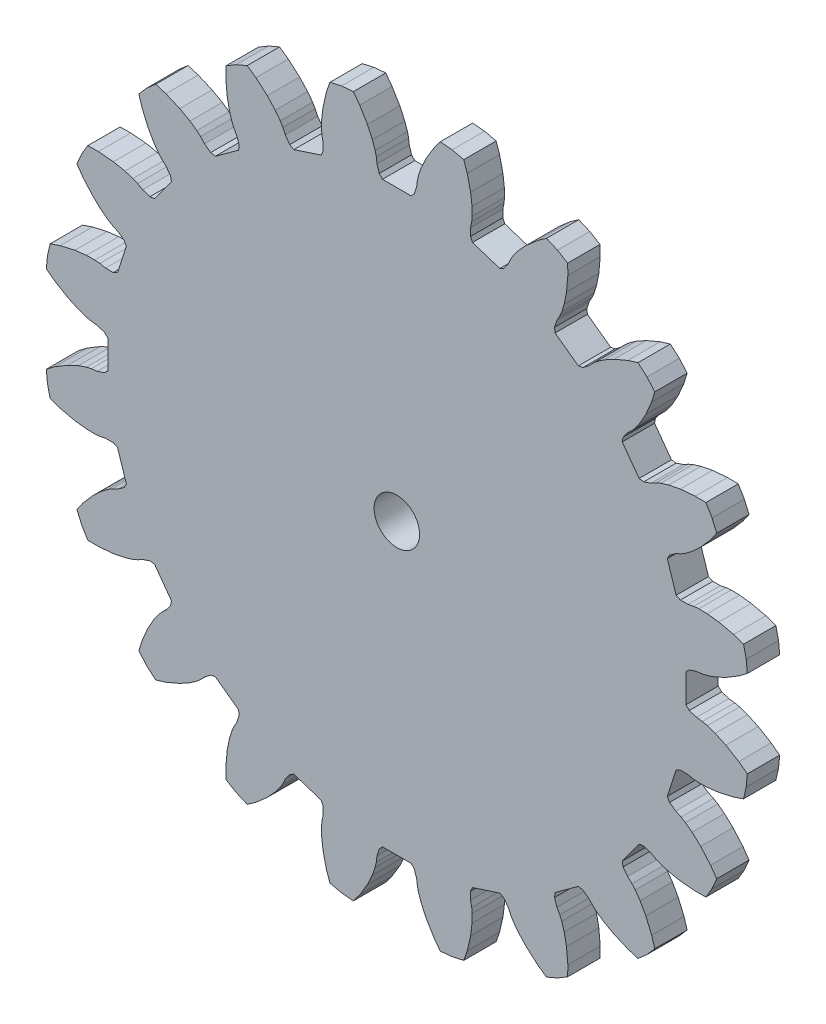
SolidWorks part; units mm, degrees
ref_plane "Front Plane" through (0, 0, 0) normal (0, 0, 1) x (1, 0, 0)
ref_plane "Top Plane" through (0, 0, 0) normal (0, 1, 0) x (1, 0, 0)
ref_plane "Right Plane" through (0, 0, 0) normal (1, 0, 0) x (0, 0, -1)
sketch "Model" plane through (0, 0, 0) normal (0, 0, 1) x (1, 0, 0)
  line L0 (-3.2331, -203.5925) -> (3.1831, -201.398)
  line L1 (3.1831, -201.398) -> (3.1831, -198.602)
  line L2 (3.1831, -198.602) -> (-3.2331, -196.4075)
  line L3 (-3.2331, -196.4075) -> (-3.2331, -193.5925)
  line L4 (-3.2331, -193.5925) -> (3.1831, -191.398)
  line L5 (3.1831, -191.398) -> (3.1831, -188.602)
  line L6 (3.1831, -188.602) -> (-3.2331, -186.4075)
  line L7 (-3.2331, -186.4075) -> (-3.2331, -183.5925)
  line L8 (-3.2331, -183.5925) -> (3.1831, -181.398)
  line L9 (3.1831, -181.398) -> (3.1831, -178.602)
  line L10 (3.1831, -178.602) -> (-3.2331, -176.4075)
  line L11 (-3.2331, -176.4075) -> (-3.2331, -173.5925)
  line L12 (-3.2331, -173.5925) -> (3.1831, -171.398)
  line L13 (3.1831, -171.398) -> (3.1831, -168.602)
  line L14 (3.1831, -168.602) -> (-3.2331, -166.4075)
  line L15 (-3.2331, -166.4075) -> (-3.2331, -163.5925)
  line L16 (-3.2331, -163.5925) -> (3.1831, -161.398)
  line L17 (3.1831, -161.398) -> (3.1831, -158.602)
  line L18 (3.1831, -158.602) -> (-3.2331, -156.4075)
  line L19 (-3.2331, -156.4075) -> (-3.2331, -153.5925)
  line L20 (-3.2331, -153.5925) -> (3.1831, -151.398)
  line L21 (3.1831, -151.398) -> (3.1831, -148.602)
  line L22 (3.1831, -148.602) -> (-3.2331, -146.4075)
  line L23 (-3.2331, -146.4075) -> (-3.2331, -143.5925)
  line L24 (-3.2331, -143.5925) -> (3.1831, -141.398)
  line L25 (3.1831, -141.398) -> (3.1831, -138.602)
  line L26 (3.1831, -138.602) -> (-3.2331, -136.4075)
  line L27 (-3.2331, -136.4075) -> (-3.2331, -133.5925)
  line L28 (-3.2331, -133.5925) -> (3.1831, -131.398)
  line L29 (3.1831, -131.398) -> (3.1831, -128.602)
  line L30 (3.1831, -128.602) -> (-3.2331, -126.4075)
  line L31 (-3.2331, -126.4075) -> (-3.2331, -123.5925)
  line L32 (-3.2331, -123.5925) -> (3.1831, -121.398)
  line L33 (3.1831, -121.398) -> (3.1831, -118.602)
  line L34 (3.1831, -118.602) -> (-3.2331, -116.4075)
  line L35 (-3.2331, -116.4075) -> (-3.2331, -113.5925)
  line L36 (-3.2331, -113.5925) -> (3.1831, -111.398)
  line L37 (3.1831, -111.398) -> (3.1831, -108.602)
  line L38 (3.1831, -108.602) -> (-3.2331, -106.4075)
  line L39 (-3.2331, -106.4075) -> (-3.2331, -103.5925)
  line L40 (-3.2331, -103.5925) -> (3.1831, -101.398)
  line L41 (3.1831, -101.398) -> (3.1831, -98.602)
  line L42 (3.1831, -98.602) -> (-3.2331, -96.4075)
  line L43 (-3.2331, -96.4075) -> (-3.2331, -93.5925)
  line L44 (-3.2331, -93.5925) -> (3.1831, -91.398)
  line L45 (3.1831, -91.398) -> (3.1831, -88.602)
  line L46 (3.1831, -88.602) -> (-3.2331, -86.4075)
  line L47 (-3.2331, -86.4075) -> (-3.2331, -83.5925)
  line L48 (-3.2331, -83.5925) -> (3.1831, -81.398)
  line L49 (3.1831, -81.398) -> (3.1831, -78.602)
  line L50 (3.1831, -78.602) -> (-3.2331, -76.4075)
  line L51 (-3.2331, -76.4075) -> (-3.2331, -73.5925)
  line L52 (-3.2331, -73.5925) -> (3.1831, -71.398)
  line L53 (3.1831, -71.398) -> (3.1831, -68.602)
  line L54 (3.1831, -68.602) -> (-3.2331, -66.4075)
  line L55 (-3.2331, -66.4075) -> (-3.2331, -63.5925)
  line L56 (-3.2331, -63.5925) -> (3.1831, -61.398)
  line L57 (3.1831, -61.398) -> (3.1831, -58.602)
  line L58 (3.1831, -58.602) -> (-3.2331, -56.4075)
  line L59 (-3.2331, -56.4075) -> (-3.2331, -53.5925)
  line L60 (-3.2331, -53.5925) -> (3.1831, -51.398)
  line L61 (3.1831, -51.398) -> (3.1831, -48.602)
  line L62 (3.1831, -48.602) -> (-3.2331, -46.4075)
  line L63 (-3.2331, -46.4075) -> (-3.2331, -43.5925)
  line L64 (-3.2331, -43.5925) -> (3.1831, -41.398)
  line L65 (3.1831, -41.398) -> (3.1831, -38.602)
  line L66 (3.1831, -38.602) -> (-3.2331, -36.4075)
  line L67 (-3.2331, -36.4075) -> (-3.2331, -33.5925)
  line L68 (-3.2331, -33.5925) -> (3.1831, -31.398)
  line L69 (3.1831, -31.398) -> (3.1831, -28.602)
  line L70 (3.1831, -28.602) -> (-3.2331, -26.4075)
  line L71 (-3.2331, -26.4075) -> (-3.2331, -23.5925)
  line L72 (-3.2331, -23.5925) -> (3.1831, -21.398)
  line L73 (3.1831, -21.398) -> (3.1831, -18.602)
  line L74 (3.1831, -18.602) -> (-3.2331, -16.4075)
  line L75 (-3.2331, -16.4075) -> (-3.2331, -13.5925)
  line L76 (-3.2331, -13.5925) -> (3.1831, -11.398)
  line L77 (3.1831, -11.398) -> (3.1831, -8.602)
  line L78 (3.1831, -8.602) -> (-3.2331, -6.4075)
  line L79 (-3.2331, -6.4075) -> (-3.2331, -3.5925)
  line L80 (-3.2331, -3.5925) -> (3.1831, -1.398)
  line L81 (3.1831, -1.398) -> (3.1831, 1.398)
  line L82 (3.1831, 1.398) -> (-3.2331, 3.5925)
  line L83 (-3.2331, 3.5925) -> (-3.2331, 6.4075)
  line L84 (-3.2331, 6.4075) -> (3.1831, 8.602)
  line L85 (3.1831, 8.602) -> (3.1831, 11.398)
  line L86 (3.1831, 11.398) -> (-3.2331, 13.5925)
  line L87 (-3.2331, 13.5925) -> (-3.2331, 16.4075)
  line L88 (-3.2331, 16.4075) -> (3.1831, 18.602)
  line L89 (3.1831, 18.602) -> (3.1831, 21.398)
  line L90 (3.1831, 21.398) -> (-3.2331, 23.5925)
  line L91 (-3.2331, 23.5925) -> (-3.2331, 26.4075)
  line L92 (-3.2331, 26.4075) -> (3.1831, 28.602)
  line L93 (3.1831, 28.602) -> (3.1831, 31.398)
  line L94 (3.1831, 31.398) -> (-3.2331, 33.5925)
  line L95 (-3.2331, 33.5925) -> (-3.2331, 36.4075)
  line L96 (-3.2331, 36.4075) -> (3.1831, 38.602)
  line L97 (3.1831, 38.602) -> (3.1831, 41.398)
  line L98 (3.1831, 41.398) -> (-3.2331, 43.5925)
  line L99 (-3.2331, 43.5925) -> (-3.2331, 46.4075)
  line L100 (-3.2331, 46.4075) -> (3.1831, 48.602)
  line L101 (3.1831, 48.602) -> (3.1831, 51.398)
  line L102 (3.1831, 51.398) -> (-3.2331, 53.5925)
  line L103 (-3.2331, 53.5925) -> (-3.2331, 56.4075)
  line L104 (-3.2331, 56.4075) -> (3.1831, 58.602)
  line L105 (3.1831, 58.602) -> (3.1831, 61.398)
  line L106 (3.1831, 61.398) -> (-3.2331, 63.5925)
  line L107 (-3.2331, 63.5925) -> (-3.2331, 66.4075)
  line L108 (-3.2331, 66.4075) -> (3.1831, 68.602)
  line L109 (3.1831, 68.602) -> (3.1831, 71.398)
  line L110 (3.1831, 71.398) -> (-3.2331, 73.5925)
  line L111 (-3.2331, 73.5925) -> (-3.2331, 76.4075)
  line L112 (-3.2331, 76.4075) -> (3.1831, 78.602)
  line L113 (3.1831, 78.602) -> (3.1831, 81.398)
  line L114 (3.1831, 81.398) -> (-3.2331, 83.5925)
  line L115 (-3.2331, 83.5925) -> (-3.2331, 86.4075)
  line L116 (-3.2331, 86.4075) -> (3.1831, 88.602)
  line L117 (3.1831, 88.602) -> (3.1831, 91.398)
  line L118 (3.1831, 91.398) -> (-3.2331, 93.5925)
  line L119 (-3.2331, 93.5925) -> (-3.2331, 96.4075)
  line L120 (-3.2331, 96.4075) -> (3.1831, 98.602)
  line L121 (3.1831, 98.602) -> (3.1831, 101.398)
  line L122 (3.1831, 101.398) -> (-3.2331, 103.5925)
  line L123 (-3.2331, 103.5925) -> (-3.2331, 106.4075)
  line L124 (-3.2331, 106.4075) -> (3.1831, 108.602)
  line L125 (3.1831, 108.602) -> (3.1831, 111.398)
  line L126 (3.1831, 111.398) -> (-3.2331, 113.5925)
  line L127 (-3.2331, 113.5925) -> (-3.2331, 116.4075)
  line L128 (-3.2331, 116.4075) -> (3.1831, 118.602)
  line L129 (3.1831, 118.602) -> (3.1831, 121.398)
  line L130 (3.1831, 121.398) -> (-3.2331, 123.5925)
  line L131 (-3.2331, 123.5925) -> (-3.2331, 126.4075)
  line L132 (-3.2331, 126.4075) -> (3.1831, 128.602)
  line L133 (3.1831, 128.602) -> (3.1831, 131.398)
  line L134 (3.1831, 131.398) -> (-3.2331, 133.5925)
  line L135 (-3.2331, 133.5925) -> (-3.2331, 136.4075)
  line L136 (-3.2331, 136.4075) -> (3.1831, 138.602)
  line L137 (3.1831, 138.602) -> (3.1831, 141.398)
  line L138 (3.1831, 141.398) -> (-3.2331, 143.5925)
  line L139 (-3.2331, 143.5925) -> (-3.2331, 146.4075)
  line L140 (-3.2331, 146.4075) -> (3.1831, 148.602)
  line L141 (3.1831, 148.602) -> (3.1831, 151.398)
  line L142 (3.1831, 151.398) -> (-3.2331, 153.5925)
  line L143 (-3.2331, 153.5925) -> (-3.2331, 156.4075)
  line L144 (-3.2331, 156.4075) -> (3.1831, 158.602)
  line L145 (3.1831, 158.602) -> (3.1831, 161.398)
  line L146 (3.1831, 161.398) -> (-3.2331, 163.5925)
  line L147 (-3.2331, 163.5925) -> (-3.2331, 166.4075)
  line L148 (-3.2331, 166.4075) -> (3.1831, 168.602)
  line L149 (3.1831, 168.602) -> (3.1831, 171.398)
  line L150 (3.1831, 171.398) -> (-3.2331, 173.5925)
  line L151 (-3.2331, 173.5925) -> (-3.2331, 176.4075)
  line L152 (-3.2331, 176.4075) -> (3.1831, 178.602)
  line L153 (3.1831, 178.602) -> (3.1831, 181.398)
  line L154 (3.1831, 181.398) -> (-3.2331, 183.5925)
  line L155 (-3.2331, 183.5925) -> (-3.2331, 186.4075)
  line L156 (-3.2331, 186.4075) -> (3.1831, 188.602)
  line L157 (3.1831, 188.602) -> (3.1831, 191.398)
  line L158 (3.1831, 191.398) -> (-3.2331, 193.5925)
  line L159 (-3.2331, 193.5925) -> (-3.2331, 196.4075)
  line L160 (-3.2331, 196.4075) -> (3.1831, 198.602)
  line L161 (3.1831, 198.602) -> (3.1831, 201.398)
  line L162 (3.1831, 201.398) -> (-3.2331, 203.5925)
  line L163 (-3.2331, 203.5925) -> (-3.2331, 205)
  line L164 (-3.2331, 205) -> (-15.9655, 205)
  line L165 (-15.9655, 205) -> (-15.9655, -205)
  line L166 (-15.9655, -205) -> (-3.2331, -205)
  line L167 (-3.2331, -205) -> (-3.2331, -203.5925)
  line L168 (-2.4761, 6.6265) -> (-2.752, 5.4774)
  line L169 (-2.752, 5.4774) -> (-2.8447, 4.2993)
  line L170 (-2.8447, 4.2993) -> (-2.0018, 3.6669)
  line L171 (-2.0018, 3.6669) -> (-0.7228, 2.9019)
  line L172 (-0.7228, 2.9019) -> (0.3292, 2.414)
  line L173 (0.3292, 2.414) -> (1.1138, 2.1457)
  line L174 (1.1138, 2.1457) -> (1.5998, 2.0345)
  line L175 (1.5998, 2.0345) -> (2.1765, 1.9649)
  line L176 (2.1765, 1.9649) -> (2.8928, 1.7388)
  line L177 (2.8928, 1.7388) -> (3.2331, 1.4208)
  line L178 (3.2331, 1.4208) -> (3.2331, -1.4208)
  line L179 (3.2331, -1.4208) -> (2.8928, -1.7388)
  line L180 (2.8928, -1.7388) -> (2.1765, -1.9649)
  line L181 (2.1765, -1.9649) -> (1.5998, -2.0345)
  line L182 (1.5998, -2.0345) -> (1.1138, -2.1457)
  line L183 (1.1138, -2.1457) -> (0.3292, -2.414)
  line L184 (0.3292, -2.414) -> (-0.7228, -2.9019)
  line L185 (-0.7228, -2.9019) -> (-2.0018, -3.6669)
  line L186 (-2.0018, -3.6669) -> (-2.8447, -4.2993)
  line L187 (-2.8447, -4.2993) -> (-2.752, -5.4774)
  line L188 (-2.752, -5.4774) -> (-2.4761, -6.6265)
  line L189 (-2.4761, -6.6265) -> (-1.4791, -6.9675)
  line L190 (-1.4791, -6.9675) -> (-0.0263, -7.2998)
  line L191 (-0.0263, -7.2998) -> (1.1251, -7.4387)
  line L192 (1.1251, -7.4387) -> (1.9541, -7.4515)
  line L193 (1.9541, -7.4515) -> (2.4507, -7.407)
  line L194 (2.4507, -7.407) -> (3.0207, -7.295)
  line L195 (3.0207, -7.295) -> (3.7718, -7.2887)
  line L196 (3.7718, -7.2887) -> (4.1937, -7.486)
  line L197 (4.1937, -7.486) -> (5.0718, -10.1885)
  line L198 (5.0718, -10.1885) -> (4.8465, -10.5961)
  line L199 (4.8465, -10.5961) -> (4.2351, -11.0325)
  line L200 (4.2351, -11.0325) -> (3.7081, -11.2769)
  line L201 (3.7081, -11.2769) -> (3.2802, -11.5328)
  line L202 (3.2802, -11.5328) -> (2.617, -12.0304)
  line L203 (2.617, -12.0304) -> (1.7672, -12.8196)
  line L204 (1.7672, -12.8196) -> (0.7872, -13.9423)
  line L205 (0.7872, -13.9423) -> (0.181, -14.8043)
  line L206 (0.181, -14.8043) -> (0.6332, -15.8961)
  line L207 (0.6332, -15.8961) -> (1.2507, -16.9037)
  line L208 (1.2507, -16.9037) -> (2.3043, -16.9199)
  line L209 (2.3043, -16.9199) -> (3.7887, -16.7869)
  line L210 (3.7887, -16.7869) -> (4.9266, -16.5633)
  line L211 (4.9266, -16.5633) -> (5.719, -16.3192)
  line L212 (5.719, -16.3192) -> (6.1775, -16.1235)
  line L213 (6.1775, -16.1235) -> (6.6851, -15.8408)
  line L214 (6.6851, -15.8408) -> (7.3975, -15.6027)
  line L215 (7.3975, -15.6027) -> (7.8597, -15.66)
  line L216 (7.8597, -15.66) -> (9.5299, -17.9589)
  line L217 (9.5299, -17.9589) -> (9.4416, -18.4162)
  line L218 (9.4416, -18.4162) -> (8.995, -19.0201)
  line L219 (8.995, -19.0201) -> (8.5693, -19.4154)
  line L220 (8.5693, -19.4154) -> (8.2414, -19.791)
  line L221 (8.2414, -19.791) -> (7.7645, -20.4692)
  line L222 (7.7645, -20.4692) -> (7.2001, -21.4824)
  line L223 (7.2001, -21.4824) -> (6.615, -22.853)
  line L224 (6.615, -22.853) -> (6.3048, -23.8601)
  line L225 (6.3048, -23.8601) -> (7.0723, -24.7587)
  line L226 (7.0723, -24.7587) -> (7.9709, -25.5262)
  line L227 (7.9709, -25.5262) -> (8.978, -25.216)
  line L228 (8.978, -25.216) -> (10.3486, -24.6309)
  line L229 (10.3486, -24.6309) -> (11.3618, -24.0665)
  line L230 (11.3618, -24.0665) -> (12.04, -23.5896)
  line L231 (12.04, -23.5896) -> (12.4155, -23.2617)
  line L232 (12.4155, -23.2617) -> (12.8109, -22.836)
  line L233 (12.8109, -22.836) -> (13.4148, -22.3894)
  line L234 (13.4148, -22.3894) -> (13.8721, -22.301)
  line L235 (13.8721, -22.301) -> (16.171, -23.9713)
  line L236 (16.171, -23.9713) -> (16.2283, -24.4335)
  line L237 (16.2283, -24.4335) -> (15.9902, -25.1459)
  line L238 (15.9902, -25.1459) -> (15.7075, -25.6535)
  line L239 (15.7075, -25.6535) -> (15.5117, -26.112)
  line L240 (15.5117, -26.112) -> (15.2677, -26.9044)
  line L241 (15.2677, -26.9044) -> (15.0441, -28.0423)
  line L242 (15.0441, -28.0423) -> (14.9111, -29.5267)
  line L243 (14.9111, -29.5267) -> (14.9273, -30.5803)
  line L244 (14.9273, -30.5803) -> (15.9349, -31.1978)
  line L245 (15.9349, -31.1978) -> (17.0267, -31.65)
  line L246 (17.0267, -31.65) -> (17.8887, -31.0438)
  line L247 (17.8887, -31.0438) -> (19.0114, -30.0638)
  line L248 (19.0114, -30.0638) -> (19.8006, -29.214)
  line L249 (19.8006, -29.214) -> (20.2982, -28.5508)
  line L250 (20.2982, -28.5508) -> (20.5541, -28.1229)
  line L251 (20.5541, -28.1229) -> (20.7985, -27.5959)
  line L252 (20.7985, -27.5959) -> (21.2349, -26.9845)
  line L253 (21.2349, -26.9845) -> (21.6425, -26.7592)
  line L254 (21.6425, -26.7592) -> (24.345, -27.6373)
  line L255 (24.345, -27.6373) -> (24.5423, -28.0592)
  line L256 (24.5423, -28.0592) -> (24.536, -28.8102)
  line L257 (24.536, -28.8102) -> (24.424, -29.3803)
  line L258 (24.424, -29.3803) -> (24.3795, -29.8769)
  line L259 (24.3795, -29.8769) -> (24.3923, -30.7059)
  line L260 (24.3923, -30.7059) -> (24.5312, -31.8573)
  line L261 (24.5312, -31.8573) -> (24.8635, -33.3101)
  line L262 (24.8635, -33.3101) -> (25.2045, -34.3071)
  line L263 (25.2045, -34.3071) -> (26.3536, -34.583)
  line L264 (26.3536, -34.583) -> (27.5317, -34.6757)
  line L265 (27.5317, -34.6757) -> (28.1641, -33.8328)
  line L266 (28.1641, -33.8328) -> (28.929, -32.5538)
  line L267 (28.929, -32.5538) -> (29.417, -31.5017)
  line L268 (29.417, -31.5017) -> (29.6853, -30.7172)
  line L269 (29.6853, -30.7172) -> (29.7965, -30.2312)
  line L270 (29.7965, -30.2312) -> (29.8661, -29.6544)
  line L271 (29.8661, -29.6544) -> (30.0922, -28.9382)
  line L272 (30.0922, -28.9382) -> (30.4102, -28.5979)
  line L273 (30.4102, -28.5979) -> (33.2518, -28.5979)
  line L274 (33.2518, -28.5979) -> (33.5698, -28.9382)
  line L275 (33.5698, -28.9382) -> (33.7959, -29.6544)
  line L276 (33.7959, -29.6544) -> (33.8655, -30.2312)
  line L277 (33.8655, -30.2312) -> (33.9767, -30.7172)
  line L278 (33.9767, -30.7172) -> (34.245, -31.5017)
  line L279 (34.245, -31.5017) -> (34.7329, -32.5538)
  line L280 (34.7329, -32.5538) -> (35.4979, -33.8328)
  line L281 (35.4979, -33.8328) -> (36.1303, -34.6757)
  line L282 (36.1303, -34.6757) -> (37.3084, -34.583)
  line L283 (37.3084, -34.583) -> (38.4575, -34.3071)
  line L284 (38.4575, -34.3071) -> (38.7985, -33.3101)
  line L285 (38.7985, -33.3101) -> (39.1308, -31.8573)
  line L286 (39.1308, -31.8573) -> (39.2697, -30.7059)
  line L287 (39.2697, -30.7059) -> (39.2825, -29.8769)
  line L288 (39.2825, -29.8769) -> (39.238, -29.3803)
  line L289 (39.238, -29.3803) -> (39.126, -28.8102)
  line L290 (39.126, -28.8102) -> (39.1197, -28.0592)
  line L291 (39.1197, -28.0592) -> (39.3169, -27.6373)
  line L292 (39.3169, -27.6373) -> (42.0195, -26.7592)
  line L293 (42.0195, -26.7592) -> (42.4271, -26.9845)
  line L294 (42.4271, -26.9845) -> (42.8635, -27.5959)
  line L295 (42.8635, -27.5959) -> (43.1079, -28.1229)
  line L296 (43.1079, -28.1229) -> (43.3638, -28.5508)
  line L297 (43.3638, -28.5508) -> (43.8614, -29.214)
  line L298 (43.8614, -29.214) -> (44.6506, -30.0638)
  line L299 (44.6506, -30.0638) -> (45.7733, -31.0438)
  line L300 (45.7733, -31.0438) -> (46.6353, -31.65)
  line L301 (46.6353, -31.65) -> (47.7271, -31.1978)
  line L302 (47.7271, -31.1978) -> (48.7347, -30.5803)
  line L303 (48.7347, -30.5803) -> (48.7509, -29.5267)
  line L304 (48.7509, -29.5267) -> (48.6179, -28.0423)
  line L305 (48.6179, -28.0423) -> (48.3943, -26.9044)
  line L306 (48.3943, -26.9044) -> (48.1502, -26.112)
  line L307 (48.1502, -26.112) -> (47.9545, -25.6535)
  line L308 (47.9545, -25.6535) -> (47.6718, -25.1459)
  line L309 (47.6718, -25.1459) -> (47.4337, -24.4335)
  line L310 (47.4337, -24.4335) -> (47.4909, -23.9713)
  line L311 (47.4909, -23.9713) -> (49.7899, -22.301)
  line L312 (49.7899, -22.301) -> (50.2472, -22.3894)
  line L313 (50.2472, -22.3894) -> (50.8511, -22.836)
  line L314 (50.8511, -22.836) -> (51.2464, -23.2617)
  line L315 (51.2464, -23.2617) -> (51.622, -23.5896)
  line L316 (51.622, -23.5896) -> (52.3002, -24.0665)
  line L317 (52.3002, -24.0665) -> (53.3134, -24.6309)
  line L318 (53.3134, -24.6309) -> (54.684, -25.216)
  line L319 (54.684, -25.216) -> (55.6911, -25.5262)
  line L320 (55.6911, -25.5262) -> (56.5897, -24.7587)
  line L321 (56.5897, -24.7587) -> (57.3572, -23.8601)
  line L322 (57.3572, -23.8601) -> (57.047, -22.853)
  line L323 (57.047, -22.853) -> (56.4619, -21.4824)
  line L324 (56.4619, -21.4824) -> (55.8975, -20.4692)
  line L325 (55.8975, -20.4692) -> (55.4206, -19.791)
  line L326 (55.4206, -19.791) -> (55.0927, -19.4154)
  line L327 (55.0927, -19.4154) -> (54.667, -19.0201)
  line L328 (54.667, -19.0201) -> (54.2204, -18.4162)
  line L329 (54.2204, -18.4162) -> (54.132, -17.9589)
  line L330 (54.132, -17.9589) -> (55.8023, -15.66)
  line L331 (55.8023, -15.66) -> (56.2645, -15.6027)
  line L332 (56.2645, -15.6027) -> (56.9769, -15.8408)
  line L333 (56.9769, -15.8408) -> (57.4844, -16.1235)
  line L334 (57.4844, -16.1235) -> (57.943, -16.3192)
  line L335 (57.943, -16.3192) -> (58.7353, -16.5633)
  line L336 (58.7353, -16.5633) -> (59.8733, -16.7869)
  line L337 (59.8733, -16.7869) -> (61.3577, -16.9199)
  line L338 (61.3577, -16.9199) -> (62.4113, -16.9037)
  line L339 (62.4113, -16.9037) -> (63.0288, -15.8961)
  line L340 (63.0288, -15.8961) -> (63.481, -14.8043)
  line L341 (63.481, -14.8043) -> (62.8748, -13.9423)
  line L342 (62.8748, -13.9423) -> (61.8948, -12.8196)
  line L343 (61.8948, -12.8196) -> (61.045, -12.0304)
  line L344 (61.045, -12.0304) -> (60.3818, -11.5328)
  line L345 (60.3818, -11.5328) -> (59.9539, -11.2769)
  line L346 (59.9539, -11.2769) -> (59.4268, -11.0325)
  line L347 (59.4268, -11.0325) -> (58.8155, -10.5961)
  line L348 (58.8155, -10.5961) -> (58.5901, -10.1885)
  line L349 (58.5901, -10.1885) -> (59.4683, -7.486)
  line L350 (59.4683, -7.486) -> (59.8901, -7.2887)
  line L351 (59.8901, -7.2887) -> (60.6412, -7.295)
  line L352 (60.6412, -7.295) -> (61.2113, -7.407)
  line L353 (61.2113, -7.407) -> (61.7079, -7.4515)
  line L354 (61.7079, -7.4515) -> (62.5369, -7.4387)
  line L355 (62.5369, -7.4387) -> (63.6883, -7.2998)
  line L356 (63.6883, -7.2998) -> (65.141, -6.9675)
  line L357 (65.141, -6.9675) -> (66.1381, -6.6265)
  line L358 (66.1381, -6.6265) -> (66.414, -5.4774)
  line L359 (66.414, -5.4774) -> (66.5067, -4.2993)
  line L360 (66.5067, -4.2993) -> (65.6638, -3.6669)
  line L361 (65.6638, -3.6669) -> (64.3848, -2.9019)
  line L362 (64.3848, -2.9019) -> (63.3327, -2.414)
  line L363 (63.3327, -2.414) -> (62.5482, -2.1457)
  line L364 (62.5482, -2.1457) -> (62.0622, -2.0345)
  line L365 (62.0622, -2.0345) -> (61.4854, -1.9649)
  line L366 (61.4854, -1.9649) -> (60.7692, -1.7388)
  line L367 (60.7692, -1.7388) -> (60.4289, -1.4208)
  line L368 (60.4289, -1.4208) -> (60.4289, 1.4208)
  line L369 (60.4289, 1.4208) -> (60.7692, 1.7388)
  line L370 (60.7692, 1.7388) -> (61.4854, 1.9649)
  line L371 (61.4854, 1.9649) -> (62.0622, 2.0345)
  line L372 (62.0622, 2.0345) -> (62.5482, 2.1457)
  line L373 (62.5482, 2.1457) -> (63.3327, 2.414)
  line L374 (63.3327, 2.414) -> (64.3848, 2.9019)
  line L375 (64.3848, 2.9019) -> (65.6638, 3.6669)
  line L376 (65.6638, 3.6669) -> (66.5067, 4.2993)
  line L377 (66.5067, 4.2993) -> (66.414, 5.4774)
  line L378 (66.414, 5.4774) -> (66.1381, 6.6265)
  line L379 (66.1381, 6.6265) -> (65.141, 6.9675)
  line L380 (65.141, 6.9675) -> (63.6883, 7.2998)
  line L381 (63.6883, 7.2998) -> (62.5369, 7.4387)
  line L382 (62.5369, 7.4387) -> (61.7079, 7.4515)
  line L383 (61.7079, 7.4515) -> (61.2113, 7.407)
  line L384 (61.2113, 7.407) -> (60.6412, 7.295)
  line L385 (60.6412, 7.295) -> (59.8901, 7.2887)
  line L386 (59.8901, 7.2887) -> (59.4683, 7.486)
  line L387 (59.4683, 7.486) -> (58.5901, 10.1885)
  line L388 (58.5901, 10.1885) -> (58.8155, 10.5961)
  line L389 (58.8155, 10.5961) -> (59.4268, 11.0325)
  line L390 (59.4268, 11.0325) -> (59.9539, 11.2769)
  line L391 (59.9539, 11.2769) -> (60.3818, 11.5328)
  line L392 (60.3818, 11.5328) -> (61.045, 12.0304)
  line L393 (61.045, 12.0304) -> (61.8948, 12.8196)
  line L394 (61.8948, 12.8196) -> (62.8748, 13.9423)
  line L395 (62.8748, 13.9423) -> (63.481, 14.8043)
  line L396 (63.481, 14.8043) -> (63.0288, 15.8961)
  line L397 (63.0288, 15.8961) -> (62.4113, 16.9037)
  line L398 (62.4113, 16.9037) -> (61.3577, 16.9199)
  line L399 (61.3577, 16.9199) -> (59.8733, 16.7869)
  line L400 (59.8733, 16.7869) -> (58.7353, 16.5633)
  line L401 (58.7353, 16.5633) -> (57.943, 16.3192)
  line L402 (57.943, 16.3192) -> (57.4844, 16.1235)
  line L403 (57.4844, 16.1235) -> (56.9769, 15.8408)
  line L404 (56.9769, 15.8408) -> (56.2645, 15.6027)
  line L405 (56.2645, 15.6027) -> (55.8023, 15.66)
  line L406 (55.8023, 15.66) -> (54.132, 17.9589)
  line L407 (54.132, 17.9589) -> (54.2204, 18.4162)
  line L408 (54.2204, 18.4162) -> (54.667, 19.0201)
  line L409 (54.667, 19.0201) -> (55.0927, 19.4154)
  line L410 (55.0927, 19.4154) -> (55.4206, 19.791)
  line L411 (55.4206, 19.791) -> (55.8975, 20.4692)
  line L412 (55.8975, 20.4692) -> (56.4619, 21.4824)
  line L413 (56.4619, 21.4824) -> (57.047, 22.853)
  line L414 (57.047, 22.853) -> (57.3572, 23.8601)
  line L415 (57.3572, 23.8601) -> (56.5897, 24.7587)
  line L416 (56.5897, 24.7587) -> (55.6911, 25.5262)
  line L417 (55.6911, 25.5262) -> (54.684, 25.216)
  line L418 (54.684, 25.216) -> (53.3134, 24.6309)
  line L419 (53.3134, 24.6309) -> (52.3002, 24.0665)
  line L420 (52.3002, 24.0665) -> (51.622, 23.5896)
  line L421 (51.622, 23.5896) -> (51.2464, 23.2617)
  line L422 (51.2464, 23.2617) -> (50.8511, 22.836)
  line L423 (50.8511, 22.836) -> (50.2472, 22.3894)
  line L424 (50.2472, 22.3894) -> (49.7899, 22.301)
  line L425 (49.7899, 22.301) -> (47.4909, 23.9713)
  line L426 (47.4909, 23.9713) -> (47.4337, 24.4335)
  line L427 (47.4337, 24.4335) -> (47.6718, 25.1459)
  line L428 (47.6718, 25.1459) -> (47.9545, 25.6535)
  line L429 (47.9545, 25.6535) -> (48.1502, 26.112)
  line L430 (48.1502, 26.112) -> (48.3943, 26.9044)
  line L431 (48.3943, 26.9044) -> (48.6179, 28.0423)
  line L432 (48.6179, 28.0423) -> (48.7509, 29.5267)
  line L433 (48.7509, 29.5267) -> (48.7347, 30.5803)
  line L434 (48.7347, 30.5803) -> (47.7271, 31.1978)
  line L435 (47.7271, 31.1978) -> (46.6353, 31.65)
  line L436 (46.6353, 31.65) -> (45.7733, 31.0438)
  line L437 (45.7733, 31.0438) -> (44.6506, 30.0638)
  line L438 (44.6506, 30.0638) -> (43.8614, 29.214)
  line L439 (43.8614, 29.214) -> (43.3638, 28.5508)
  line L440 (43.3638, 28.5508) -> (43.1079, 28.1229)
  line L441 (43.1079, 28.1229) -> (42.8635, 27.5959)
  line L442 (42.8635, 27.5959) -> (42.4271, 26.9845)
  line L443 (42.4271, 26.9845) -> (42.0195, 26.7592)
  line L444 (42.0195, 26.7592) -> (39.3169, 27.6373)
  line L445 (39.3169, 27.6373) -> (39.1197, 28.0592)
  line L446 (39.1197, 28.0592) -> (39.126, 28.8102)
  line L447 (39.126, 28.8102) -> (39.238, 29.3803)
  line L448 (39.238, 29.3803) -> (39.2825, 29.8769)
  line L449 (39.2825, 29.8769) -> (39.2697, 30.7059)
  line L450 (39.2697, 30.7059) -> (39.1308, 31.8573)
  line L451 (39.1308, 31.8573) -> (38.7985, 33.3101)
  line L452 (38.7985, 33.3101) -> (38.4575, 34.3071)
  line L453 (38.4575, 34.3071) -> (37.3084, 34.583)
  line L454 (37.3084, 34.583) -> (36.1303, 34.6757)
  line L455 (36.1303, 34.6757) -> (35.4979, 33.8328)
  line L456 (35.4979, 33.8328) -> (34.7329, 32.5538)
  line L457 (34.7329, 32.5538) -> (34.245, 31.5017)
  line L458 (34.245, 31.5017) -> (33.9767, 30.7172)
  line L459 (33.9767, 30.7172) -> (33.8655, 30.2312)
  line L460 (33.8655, 30.2312) -> (33.7959, 29.6544)
  line L461 (33.7959, 29.6544) -> (33.5698, 28.9382)
  line L462 (33.5698, 28.9382) -> (33.2518, 28.5979)
  line L463 (33.2518, 28.5979) -> (30.4102, 28.5979)
  line L464 (30.4102, 28.5979) -> (30.0922, 28.9382)
  line L465 (30.0922, 28.9382) -> (29.8661, 29.6544)
  line L466 (29.8661, 29.6544) -> (29.7965, 30.2312)
  line L467 (29.7965, 30.2312) -> (29.6853, 30.7172)
  line L468 (29.6853, 30.7172) -> (29.417, 31.5017)
  line L469 (29.417, 31.5017) -> (28.929, 32.5538)
  line L470 (28.929, 32.5538) -> (28.1641, 33.8328)
  line L471 (28.1641, 33.8328) -> (27.5317, 34.6757)
  line L472 (27.5317, 34.6757) -> (26.3536, 34.583)
  line L473 (26.3536, 34.583) -> (25.2045, 34.3071)
  line L474 (25.2045, 34.3071) -> (24.8635, 33.3101)
  line L475 (24.8635, 33.3101) -> (24.5312, 31.8573)
  line L476 (24.5312, 31.8573) -> (24.3923, 30.7059)
  line L477 (24.3923, 30.7059) -> (24.3795, 29.8769)
  line L478 (24.3795, 29.8769) -> (24.424, 29.3803)
  line L479 (24.424, 29.3803) -> (24.536, 28.8102)
  line L480 (24.536, 28.8102) -> (24.5423, 28.0592)
  line L481 (24.5423, 28.0592) -> (24.345, 27.6373)
  line L482 (24.345, 27.6373) -> (21.6425, 26.7592)
  line L483 (21.6425, 26.7592) -> (21.2349, 26.9845)
  line L484 (21.2349, 26.9845) -> (20.7985, 27.5959)
  line L485 (20.7985, 27.5959) -> (20.5541, 28.1229)
  line L486 (20.5541, 28.1229) -> (20.2982, 28.5508)
  line L487 (20.2982, 28.5508) -> (19.8006, 29.214)
  line L488 (19.8006, 29.214) -> (19.0114, 30.0638)
  line L489 (19.0114, 30.0638) -> (17.8887, 31.0438)
  line L490 (17.8887, 31.0438) -> (17.0267, 31.65)
  line L491 (17.0267, 31.65) -> (15.9349, 31.1978)
  line L492 (15.9349, 31.1978) -> (14.9273, 30.5803)
  line L493 (14.9273, 30.5803) -> (14.9111, 29.5267)
  line L494 (14.9111, 29.5267) -> (15.0441, 28.0423)
  line L495 (15.0441, 28.0423) -> (15.2677, 26.9044)
  line L496 (15.2677, 26.9044) -> (15.5117, 26.112)
  line L497 (15.5117, 26.112) -> (15.7075, 25.6535)
  line L498 (15.7075, 25.6535) -> (15.9902, 25.1459)
  line L499 (15.9902, 25.1459) -> (16.2283, 24.4335)
  line L500 (16.2283, 24.4335) -> (16.171, 23.9713)
  line L501 (16.171, 23.9713) -> (13.8721, 22.301)
  line L502 (13.8721, 22.301) -> (13.4148, 22.3894)
  line L503 (13.4148, 22.3894) -> (12.8109, 22.836)
  line L504 (12.8109, 22.836) -> (12.4155, 23.2617)
  line L505 (12.4155, 23.2617) -> (12.04, 23.5896)
  line L506 (12.04, 23.5896) -> (11.3618, 24.0665)
  line L507 (11.3618, 24.0665) -> (10.3486, 24.6309)
  line L508 (10.3486, 24.6309) -> (8.978, 25.216)
  line L509 (8.978, 25.216) -> (7.9709, 25.5262)
  line L510 (7.9709, 25.5262) -> (7.0723, 24.7587)
  line L511 (7.0723, 24.7587) -> (6.3048, 23.8601)
  line L512 (6.3048, 23.8601) -> (6.615, 22.853)
  line L513 (6.615, 22.853) -> (7.2001, 21.4824)
  line L514 (7.2001, 21.4824) -> (7.7645, 20.4692)
  line L515 (7.7645, 20.4692) -> (8.2414, 19.791)
  line L516 (8.2414, 19.791) -> (8.5693, 19.4154)
  line L517 (8.5693, 19.4154) -> (8.995, 19.0201)
  line L518 (8.995, 19.0201) -> (9.4416, 18.4162)
  line L519 (9.4416, 18.4162) -> (9.5299, 17.9589)
  line L520 (9.5299, 17.9589) -> (7.8597, 15.66)
  line L521 (7.8597, 15.66) -> (7.3975, 15.6027)
  line L522 (7.3975, 15.6027) -> (6.6851, 15.8408)
  line L523 (6.6851, 15.8408) -> (6.1775, 16.1235)
  line L524 (6.1775, 16.1235) -> (5.719, 16.3192)
  line L525 (5.719, 16.3192) -> (4.9266, 16.5633)
  line L526 (4.9266, 16.5633) -> (3.7887, 16.7869)
  line L527 (3.7887, 16.7869) -> (2.3043, 16.9199)
  line L528 (2.3043, 16.9199) -> (1.2507, 16.9037)
  line L529 (1.2507, 16.9037) -> (0.6332, 15.8961)
  line L530 (0.6332, 15.8961) -> (0.181, 14.8043)
  line L531 (0.181, 14.8043) -> (0.7872, 13.9423)
  line L532 (0.7872, 13.9423) -> (1.7672, 12.8196)
  line L533 (1.7672, 12.8196) -> (2.617, 12.0304)
  line L534 (2.617, 12.0304) -> (3.2802, 11.5328)
  line L535 (3.2802, 11.5328) -> (3.7081, 11.2769)
  line L536 (3.7081, 11.2769) -> (4.2351, 11.0325)
  line L537 (4.2351, 11.0325) -> (4.8465, 10.5961)
  line L538 (4.8465, 10.5961) -> (5.0718, 10.1885)
  line L539 (5.0718, 10.1885) -> (4.1937, 7.486)
  line L540 (4.1937, 7.486) -> (3.7718, 7.2887)
  line L541 (3.7718, 7.2887) -> (3.0207, 7.295)
  line L542 (3.0207, 7.295) -> (2.4507, 7.407)
  line L543 (2.4507, 7.407) -> (1.9541, 7.4515)
  line L544 (1.9541, 7.4515) -> (1.1251, 7.4387)
  line L545 (1.1251, 7.4387) -> (-0.0263, 7.2998)
  line L546 (-0.0263, 7.2998) -> (-1.4791, 6.9675)
  line L547 (-1.4791, 6.9675) -> (-2.4761, 6.6265)
  line L548 (31.0247, 2.1006) -> (31.479, 2.2223)
  line L549 (31.479, 2.2223) -> (31.9487, 2.2469)
  line L550 (31.9487, 2.2469) -> (32.4133, 2.1733)
  line L551 (32.4133, 2.1733) -> (32.8525, 2.0048)
  line L552 (32.8525, 2.0048) -> (33.247, 1.7486)
  line L553 (33.247, 1.7486) -> (33.5796, 1.416)
  line L554 (33.5796, 1.416) -> (33.8358, 1.0215)
  line L555 (33.8358, 1.0215) -> (34.0043, 0.5823)
  line L556 (34.0043, 0.5823) -> (34.0779, 0.1178)
  line L557 (34.0779, 0.1178) -> (34.0533, -0.352)
  line L558 (34.0533, -0.352) -> (33.9315, -0.8063)
  line L559 (33.9315, -0.8063) -> (33.718, -1.2254)
  line L560 (33.718, -1.2254) -> (33.422, -1.591)
  line L561 (33.422, -1.591) -> (33.0564, -1.887)
  line L562 (33.0564, -1.887) -> (32.6373, -2.1006)
  line L563 (32.6373, -2.1006) -> (32.183, -2.2223)
  line L564 (32.183, -2.2223) -> (31.7132, -2.2469)
  line L565 (31.7132, -2.2469) -> (31.2486, -2.1733)
  line L566 (31.2486, -2.1733) -> (30.8095, -2.0048)
  line L567 (30.8095, -2.0048) -> (30.415, -1.7486)
  line L568 (30.415, -1.7486) -> (30.0824, -1.416)
  line L569 (30.0824, -1.416) -> (29.8262, -1.0215)
  line L570 (29.8262, -1.0215) -> (29.6577, -0.5823)
  line L571 (29.6577, -0.5823) -> (29.5841, -0.1178)
  line L572 (29.5841, -0.1178) -> (29.6087, 0.352)
  line L573 (29.6087, 0.352) -> (29.7304, 0.8063)
  line L574 (29.7304, 0.8063) -> (29.944, 1.2254)
  line L575 (29.944, 1.2254) -> (30.24, 1.591)
  line L576 (30.24, 1.591) -> (30.6056, 1.887)
  line L577 (30.6056, 1.887) -> (31.0247, 2.1006)
sketch "gear_body" plane through (0, 0, 0) normal (0, 0, 1) x (1, 0, 0)
  line L0 (0, 0) -> (31.831, 0) construction
  circle A0 centre (31.831, 0) radius 2.25
  circle A1 centre (31.831, 0) radius 31.831 construction
  circle A2 centre (31.831, 0) radius 35
  dimension "D1" = 31.831
  dimension "D2" = 70
  dimension "D3" = 4.5
sketch "rack" plane through (0, 0, 0) normal (0, 0, 1) x (1, 0, 0)
  line L0 (0, 0) -> (3.1831, 0) construction
  line L1 (0, 0) -> (31.831, 0) construction
  line L2 (-3.2331, -6.4075) -> (-3.2331, 96.4075) construction
  line L3 (-3.2331, -3.5925) -> (-3.2331, -6.4075)
  line L4 (0, -6.4075) -> (0, 96.4075) construction
  line L5 (3.1831, -6.4075) -> (3.1831, 96.4075) construction
  line L6 (-3.2331, -6.4075) -> (3.1831, -6.4075) construction
  line L7 (-3.2331, -3.5925) -> (3.1831, -1.398)
  line L8 (3.1831, -1.398) -> (3.1831, 1.398)
  line L9 (3.1831, 1.398) -> (-3.2331, 3.5925)
  line L10 (-3.2331, 3.5925) -> (-3.2331, 6.4075)
  line L11 (-3.2331, 96.4075) -> (3.1831, 96.4075) construction
  line L12 (-3.2331, 13.5925) -> (-3.2331, 16.4075)
  line L13 (3.1831, 11.398) -> (-3.2331, 13.5925)
  line L14 (3.1831, 8.602) -> (3.1831, 11.398)
  line L15 (-3.2331, 6.4075) -> (3.1831, 8.602)
  line L16 (-3.2331, 23.5925) -> (-3.2331, 26.4075)
  line L17 (3.1831, 21.398) -> (-3.2331, 23.5925)
  line L18 (3.1831, 18.602) -> (3.1831, 21.398)
  line L19 (-3.2331, 16.4075) -> (3.1831, 18.602)
  line L20 (-3.2331, 33.5925) -> (-3.2331, 36.4075)
  line L21 (3.1831, 31.398) -> (-3.2331, 33.5925)
  line L22 (3.1831, 28.602) -> (3.1831, 31.398)
  line L23 (-3.2331, 26.4075) -> (3.1831, 28.602)
  line L24 (-3.2331, 43.5925) -> (-3.2331, 46.4075)
  line L25 (3.1831, 41.398) -> (-3.2331, 43.5925)
  line L26 (3.1831, 38.602) -> (3.1831, 41.398)
  line L27 (-3.2331, 36.4075) -> (3.1831, 38.602)
  line L28 (-3.2331, 53.5925) -> (-3.2331, 56.4075)
  line L29 (3.1831, 51.398) -> (-3.2331, 53.5925)
  line L30 (3.1831, 48.602) -> (3.1831, 51.398)
  line L31 (-3.2331, 46.4075) -> (3.1831, 48.602)
  line L32 (-3.2331, 63.5925) -> (-3.2331, 66.4075)
  line L33 (3.1831, 61.398) -> (-3.2331, 63.5925)
  line L34 (3.1831, 58.602) -> (3.1831, 61.398)
  line L35 (-3.2331, 56.4075) -> (3.1831, 58.602)
  line L36 (-3.2331, 73.5925) -> (-3.2331, 76.4075)
  line L37 (3.1831, 71.398) -> (-3.2331, 73.5925)
  line L38 (3.1831, 68.602) -> (3.1831, 71.398)
  line L39 (-3.2331, 66.4075) -> (3.1831, 68.602)
  line L40 (-3.2331, 83.5925) -> (-3.2331, 86.4075)
  line L41 (3.1831, 81.398) -> (-3.2331, 83.5925)
  line L42 (3.1831, 78.602) -> (3.1831, 81.398)
  line L43 (-3.2331, 76.4075) -> (3.1831, 78.602)
  line L44 (-3.2331, 93.5925) -> (-3.2331, 96.4075)
  line L45 (3.1831, 91.398) -> (-3.2331, 93.5925)
  line L46 (3.1831, 88.602) -> (3.1831, 91.398)
  line L47 (-3.2331, 86.4075) -> (3.1831, 88.602)
  line L48 (3.1831, -6.4075) -> (31.831, -6.4075) construction
  line L49 (31.831, -6.4075) -> (31.831, 96.4075) construction
  line L50 (31.831, 96.4075) -> (3.1831, 96.4075) construction
  line L51 (31.831, -6.4075) -> (66.8951, -6.4075) construction
  line L52 (31.831, 45) -> (-3.2331, 45) construction
  line L53 (66.8951, -6.4075) -> (66.8951, 96.4075)
  line L54 (31.831, -6.4075) -> (31.831, -41.4716) construction
  line L55 (31.831, 96.4075) -> (31.831, 131.4716) construction
  arc A0 (-3.2331, -6.4075) -> (66.8951, -6.4075) centre (31.831, -6.4075) ccw
  arc A1 (-3.2331, 96.4075) -> (66.8951, 96.4075) centre (31.831, 96.4075) cw
  dimension "D1" = 3.2331
  dimension "D2" = 6.4162
  dimension "D3" = 10
  dimension "D4" = 108.882
  dimension "D5" = 2.796
  dimension "D6" = 10
  dimension "D7" = 172.9432
  dimension "D8" = 70.1282
sketch "tooth_cut" plane through (0, 0, 0) normal (0, 0, 1) x (1, 0, 0)
  line L0 (0, 0) -> (31.831, 0) construction
  line L1 (3.2331, 1.4208) -> (3.2331, -1.4208)
  line L2 (31.831, 0) -> (-2.7381, 5.4752) construction
  line L3 (31.831, 0) -> (-2.7381, -5.4752) construction
  line L4 (3.2331, 1.4208) -> (2.8928, 1.7388)
  line L5 (2.8928, 1.7388) -> (2.1765, 1.9649)
  line L6 (2.1765, 1.9649) -> (1.5998, 2.0345)
  line L7 (1.5998, 2.0345) -> (1.1138, 2.1457)
  line L8 (1.1138, 2.1457) -> (0.3292, 2.414)
  line L9 (0.3292, 2.414) -> (-0.7228, 2.9019)
  line L10 (-0.7228, 2.9019) -> (-2.0018, 3.6669)
  line L11 (-2.0018, 3.6669) -> (-2.8447, 4.2993)
  line L12 (-2.8447, 4.2993) -> (-2.7381, 5.4752)
  line L13 (3.2331, -1.4208) -> (2.8928, -1.7388)
  line L14 (2.8928, -1.7388) -> (2.1765, -1.9649)
  line L15 (2.1765, -1.9649) -> (1.5998, -2.0345)
  line L16 (1.5998, -2.0345) -> (1.1138, -2.1457)
  line L17 (1.1138, -2.1457) -> (0.3292, -2.414)
  line L18 (0.3292, -2.414) -> (-0.7228, -2.9019)
  line L19 (-0.7228, -2.9019) -> (-2.0018, -3.6669)
  line L20 (-2.0018, -3.6669) -> (-2.8447, -4.2993)
  line L21 (-2.8447, -4.2993) -> (-2.7381, -5.4752)
  arc A0 (-2.7381, 5.4752) -> (-2.7381, -5.4752) centre (31.831, 0) ccw
  circle A1 centre (31.831, 0) radius 35 construction
  dimension "D3" = 18
ref_axis "Axis1" through (31.831, 0, 0) along (0, 0, 1)
sketch "Sketch5" plane through (0, 0, 0) normal (0, 0, 1) x (1, 0, 0)
  circle A0 centre (31.831, 0) radius 35
  circle A1 centre (31.831, 0) radius 35 construction
  circle A2 centre (31.831, 0) radius 2.25
  circle A3 centre (31.831, 0) radius 2.25 construction
extrude "Boss-Extrude1" add sketch "Sketch5" along normal blind 3.2
extrude "Cut-Extrude1" cut sketch "tooth_cut" along normal through all
pattern_circular "CirPattern1" count 20 over 360 about axis through (31.831, 0, 0) along (0, 0, 1) of "Cut-Extrude1"
ref_plane "Plane1" through (31.831, 0, 0) normal (1, 0, 0) x (0, 0, -1)
sketch "Sketch6" plane through (0, 0, 0) normal (0, 0, 1) x (1, 0, 0)
  line L0 (31.831, 0) -> (31.831, 96.4075) construction
  line L1 (-28.2331, -56.4716) -> (91.8951, -56.4716)
  line L2 (-38.2331, -46.4716) -> (-38.2331, 86.4075)
  line L3 (-28.2331, 96.4075) -> (-5.2331, 96.4075)
  line L4 (101.8951, -46.4716) -> (101.8951, 86.4075)
  line L5 (31.831, 96.4075) -> (31.831, 131.4716) construction
  line L6 (66.8951, -6.4075) -> (66.8951, 96.4075) construction
  line L7 (66.8951, -6.4075) -> (66.8951, 94.4075)
  line L8 (-3.2331, -6.4075) -> (-3.2331, -3.5925)
  line L9 (68.8951, 96.4075) -> (91.8951, 96.4075)
  line L10 (-18.2331, 96.4075) -> (-18.2331, -56.4716) construction
  line L11 (81.8951, -56.4716) -> (81.8951, 96.4075) construction
  line L12 (3.1831, 91.398) -> (-3.2331, 93.5925) construction
  line L13 (3.1831, 88.602) -> (3.1831, 91.398) construction
  line L14 (-3.2331, 86.4075) -> (3.1831, 88.602) construction
  line L15 (3.1831, 81.398) -> (-3.2331, 83.5925) construction
  line L16 (3.1831, 78.602) -> (3.1831, 81.398) construction
  line L17 (-3.2331, 76.4075) -> (3.1831, 78.602) construction
  line L18 (3.1831, 71.398) -> (-3.2331, 73.5925) construction
  line L19 (3.1831, 68.602) -> (3.1831, 71.398) construction
  line L20 (-3.2331, 66.4075) -> (3.1831, 68.602) construction
  line L21 (3.1831, 61.398) -> (-3.2331, 63.5925) construction
  line L22 (3.1831, 58.602) -> (3.1831, 61.398) construction
  line L23 (-3.2331, 56.4075) -> (3.1831, 58.602) construction
  line L24 (3.1831, 51.398) -> (-3.2331, 53.5925) construction
  line L25 (3.1831, 48.602) -> (3.1831, 51.398) construction
  line L26 (-3.2331, 46.4075) -> (3.1831, 48.602) construction
  line L27 (3.1831, 41.398) -> (-3.2331, 43.5925) construction
  line L28 (3.1831, 38.602) -> (3.1831, 41.398) construction
  line L29 (-3.2331, 36.4075) -> (3.1831, 38.602) construction
  line L30 (3.1831, 31.398) -> (-3.2331, 33.5925) construction
  line L31 (3.1831, 28.602) -> (3.1831, 31.398) construction
  line L32 (-3.2331, 26.4075) -> (3.1831, 28.602) construction
  line L33 (3.1831, 21.398) -> (-3.2331, 23.5925) construction
  line L34 (-3.2331, 16.4075) -> (3.1831, 18.602) construction
  line L35 (3.1831, 11.398) -> (-3.2331, 13.5925) construction
  line L36 (-3.2331, 6.4075) -> (3.1831, 8.602) construction
  line L37 (3.1831, 8.602) -> (3.1831, 11.398) construction
  line L38 (3.1831, 18.602) -> (3.1831, 21.398) construction
  line L39 (3.1831, 1.398) -> (-3.2331, 3.5925) construction
  line L40 (-3.2331, -3.5925) -> (3.1831, -1.398) construction
  line L41 (3.1831, -1.398) -> (3.1831, 1.398) construction
  line L42 (3.1831, 91.398) -> (-3.2331, 93.5925)
  line L43 (3.1831, 88.602) -> (3.1831, 91.398)
  line L44 (-3.2331, 86.4075) -> (3.1831, 88.602)
  line L45 (3.1831, 81.398) -> (-3.2331, 83.5925)
  line L46 (3.1831, 78.602) -> (3.1831, 81.398)
  line L47 (-3.2331, 76.4075) -> (3.1831, 78.602)
  line L48 (3.1831, 71.398) -> (-3.2331, 73.5925)
  line L49 (3.1831, 68.602) -> (3.1831, 71.398)
  line L50 (-3.2331, 66.4075) -> (3.1831, 68.602)
  line L51 (3.1831, 61.398) -> (-3.2331, 63.5925)
  line L52 (3.1831, 58.602) -> (3.1831, 61.398)
  line L53 (-3.2331, 56.4075) -> (3.1831, 58.602)
  line L54 (3.1831, 51.398) -> (-3.2331, 53.5925)
  line L55 (3.1831, 48.602) -> (3.1831, 51.398)
  line L56 (-3.2331, 46.4075) -> (3.1831, 48.602)
  line L57 (3.1831, 41.398) -> (-3.2331, 43.5925)
  line L58 (3.1831, 38.602) -> (3.1831, 41.398)
  line L59 (-3.2331, 36.4075) -> (3.1831, 38.602)
  line L60 (3.1831, 31.398) -> (-3.2331, 33.5925)
  line L61 (3.1831, 28.602) -> (3.1831, 31.398)
  line L62 (-3.2331, 26.4075) -> (3.1831, 28.602)
  line L63 (3.1831, 21.398) -> (-3.2331, 23.5925)
  line L64 (-3.2331, 16.4075) -> (3.1831, 18.602)
  line L65 (3.1831, 11.398) -> (-3.2331, 13.5925)
  line L66 (-3.2331, 6.4075) -> (3.1831, 8.602)
  line L67 (3.1831, 8.602) -> (3.1831, 11.398)
  line L68 (3.1831, 18.602) -> (3.1831, 21.398)
  line L69 (3.1831, 1.398) -> (-3.2331, 3.5925)
  line L70 (-3.2331, -3.5925) -> (3.1831, -1.398)
  line L71 (3.1831, -1.398) -> (3.1831, 1.398)
  line L72 (-3.2331, 3.5925) -> (-3.2331, 6.4075)
  line L73 (-3.2331, 13.5925) -> (-3.2331, 16.4075)
  line L74 (-3.2331, 23.5925) -> (-3.2331, 26.4075)
  line L75 (-3.2331, 33.5925) -> (-3.2331, 36.4075)
  line L76 (-3.2331, 93.5925) -> (-3.2331, 94.4075)
  line L77 (-3.2331, 83.5925) -> (-3.2331, 86.4075)
  line L78 (-3.2331, 73.5925) -> (-3.2331, 76.4075)
  line L79 (-3.2331, 63.5925) -> (-3.2331, 66.4075)
  line L80 (-3.2331, 53.5925) -> (-3.2331, 56.4075)
  line L81 (-3.2331, 43.5925) -> (-3.2331, 46.4075)
  arc A0 (-3.2331, -6.4075) -> (66.8951, -6.4075) centre (31.831, -6.4075) ccw construction
  arc A1 (-3.2331, -6.4075) -> (66.8951, -6.4075) centre (31.831, -6.4075) ccw
  arc A2 (91.8951, -56.4716) -> (101.8951, -46.4716) centre (91.8951, -46.4716) ccw
  arc A3 (101.8951, 86.4075) -> (91.8951, 96.4075) centre (91.8951, 86.4075) ccw
  arc A4 (-28.2331, 96.4075) -> (-38.2331, 86.4075) centre (-28.2331, 86.4075) ccw
  arc A5 (-38.2331, -46.4716) -> (-28.2331, -56.4716) centre (-28.2331, -46.4716) ccw
  arc A6 (68.8951, 96.4075) -> (66.8951, 94.4075) centre (68.8951, 94.4075) ccw
  arc A7 (-3.2331, 94.4075) -> (-5.2331, 96.4075) centre (-5.2331, 94.4075) ccw
  point P74 (-3.2331, 96.4075)
  dimension "D4" = 10
  dimension "D5" = 2
  dimension "D1" = 15
  dimension "D2" = 20
  dimension "D3" = 15
